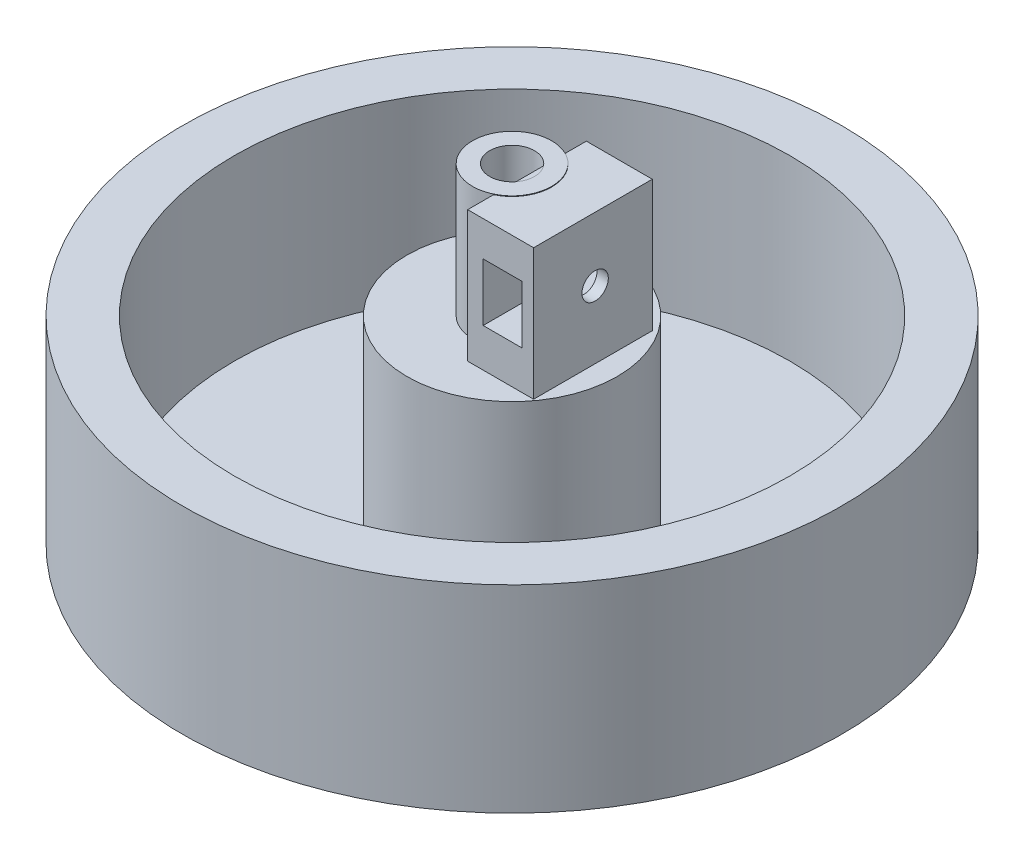
SolidWorks part; units mm, degrees
ref_plane "Front Plane" through (0, 0, 0) normal (0, 0, 1) x (1, 0, 0)
ref_plane "Top Plane" through (0, 0, 0) normal (0, 1, 0) x (1, 0, 0)
ref_plane "Right Plane" through (0, 0, 0) normal (1, 0, 0) x (0, 0, -1)
sketch "Sketch1" plane through (0, 0, 0) normal (0, 1, 0) x (1, 0, 0)
  circle A0 centre (0, 0) radius 6
extrude "Boss-Extrude1" add sketch "Sketch1" along normal blind 20
sketch "Sketch2" plane through (0, 20, 0) normal (0, 1, 0) x (1, 0, 0)
  circle A0 centre (0, 0) radius 3.4
extrude "Cut-Extrude1" cut sketch "Sketch2" against normal blind 13.55 contours A0
ref_plane "Plane1" through (0, 18.26, 0) normal (0, 1, 0) x (1, 0, 0)
ref_axis "Axis1" through (0, 6.45, 0) along (0, 1, 0)
ref_point "Point2"
sketch "Sketch5" plane through (0, 18.26, 0) normal (0, 1, 0) x (1, 0, 0)
  line L0 (0, 0) -> (2.6, 0) construction
  line L2 (2.6, -3.5716) -> (4.1507, -3.5716)
  line L3 (2.6, -3.5716) -> (2.6, 3.6126)
  line L4 (2.6, 3.6126) -> (4.1507, 3.6126)
  line L5 (4.1507, -3.5716) -> (4.1507, 3.6126)
extrude "Boss-Extrude2" add sketch "Sketch5" against normal blind 13.55
sketch "Sketch7" plane through (2.6, 0, 0) normal (-1, 0, 0) x (0, 0, 1)
  line L1 (-8.6717, 19.91) -> (9.3323, 19.91)
  line L2 (-8.6717, 19.91) -> (-8.6717, 0)
  line L3 (-8.6717, 0) -> (9.3323, 0)
  line L4 (9.3323, 19.91) -> (9.3323, 0)
extrude "Boss-Extrude3" add sketch "Sketch7" against normal blind 10
sketch "Sketch6" plane through (2.6, 0, 0) normal (-1, 0, 0) x (0, 0, 1)
  line L1 (-2.1909, 6.45) -> (-2.1909, 19.91) construction
  line L2 (2.1909, 19.91) -> (2.1909, 6.45) construction
  line L3 (-2.1909, 15.4522) -> (2.1909, 15.4522) construction
  circle A0 centre (0, 10.2369) radius 2
extrude "Cut-Extrude2" cut sketch "Sketch6" against normal blind 13.55 and the other way blind 1
ref_axis "Axis2" through (-1.8994, 10.2369, 0) along (-1, 0, 0)
ref_axis "Axis4" through (12.6, 10.2369, 0) along (-1, 0, 0)
ref_plane "Plane3" through (0, 0, 0) normal (0, 0, 1) x (1, 0, 0)
sketch "Sketch9" plane through (0, 0, 0) normal (0, 0, 1) x (1, 0, 0)
  line L0 (10.8765, 10.2369) -> (10.8765, 5.8619)
  line L1 (4.9434, 5.8619) -> (10.8765, 5.8619)
  line L2 (4.9434, 5.8619) -> (4.9434, 10.2369)
  line L3 (4.9434, 10.2369) -> (4.9434, 14.6143)
  line L4 (4.9434, 14.6143) -> (10.8765, 14.6143)
  line L5 (10.8765, 14.6143) -> (10.8765, 10.2369)
  line L6 (12.6, 10.2369) -> (2.6, 10.2369) construction
  point P5 (10.8765, 14.6143)
extrude "Cut-Extrude3" cut sketch "Sketch9" against normal blind 10 and the other way blind 10
sketch "Sketch10" plane through (0, 0, 0) normal (0, -1, 0) x (1, 0, 0)
  circle A0 centre (0, 0) radius 50
extrude "Boss-Extrude4" add sketch "Sketch10" along normal blind 30
sketch "Sketch11" plane through (0, 0, 0) normal (0, 1, 0) x (1, 0, 0)
  line L1 (31.7817, 38.8528) -> (14.4942, 48.0577) construction
  line L2 (14.4942, 48.0577) -> (-5, 49.9462) construction
  line L3 (-5, 49.9462) -> (-23.733, 44.2308) construction
  line L4 (-23.733, 44.2308) -> (-38.8528, 31.7817) construction
  line L5 (-38.8528, 31.7817) -> (-48.0577, 14.4942) construction
  line L6 (-48.0577, 14.4942) -> (-49.9462, -5) construction
  line L7 (-49.9462, -5) -> (-44.2308, -23.733) construction
  line L8 (-44.2308, -23.733) -> (-31.7817, -38.8528) construction
  line L9 (-31.7817, -38.8528) -> (-14.4942, -48.0577) construction
  line L10 (-14.4942, -48.0577) -> (5, -49.9462) construction
  line L11 (5, -49.9462) -> (23.733, -44.2308) construction
  line L12 (23.733, -44.2308) -> (38.8528, -31.7817) construction
  line L13 (38.8528, -31.7817) -> (48.0577, -14.4942) construction
  line L14 (48.0577, -14.4942) -> (49.9462, 5) construction
  line L15 (49.9462, 5) -> (44.2308, 23.733) construction
  line L16 (44.2308, 23.733) -> (31.7817, 38.8528) construction
  circle A0 centre (0, 0) radius 49.2313 construction
  circle A1 centre (5, -49.9462) radius 5
  circle A2 centre (-14.4942, -48.0577) radius 5
  circle A3 centre (-31.7817, -38.8528) radius 5
  circle A4 centre (-44.2308, -23.733) radius 5
  circle A5 centre (-49.9462, -5) radius 5
  circle A6 centre (-48.0577, 14.4942) radius 5
  circle A7 centre (-38.8528, 31.7817) radius 5
  circle A8 centre (-23.733, 44.2308) radius 5
  circle A9 centre (-5, 49.9462) radius 5
  circle A10 centre (14.4942, 48.0577) radius 5
  circle A11 centre (31.7817, 38.8528) radius 5
  circle A12 centre (44.2308, 23.733) radius 5
  circle A13 centre (49.9462, 5) radius 5
  circle A14 centre (48.0577, -14.4942) radius 5
  circle A15 centre (38.8528, -31.7817) radius 5
  circle A16 centre (23.733, -44.2308) radius 5
sketch "Sketch12" plane through (0, 0, 0) normal (0, 1, 0) x (1, 0, 0)
  circle A0 centre (0, 0) radius 42.1244
  circle A1 centre (0, 0) radius 15.9579
extrude "Cut-Extrude5" cut sketch "Sketch12" against normal blind 27
